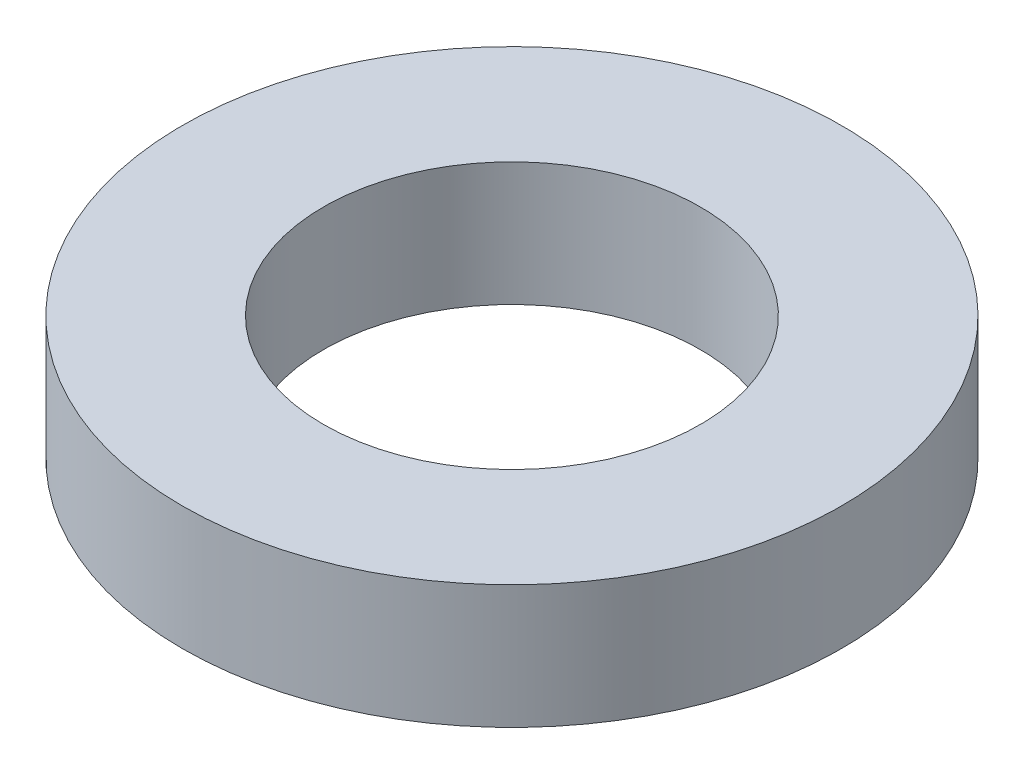
SolidWorks part; units mm, degrees
ref_plane "Front" through (0, 0, 0) normal (0, 0, 1) x (1, 0, 0)
ref_plane "Top" through (0, 0, 0) normal (0, 1, 0) x (1, 0, 0)
ref_plane "Right" through (0, 0, 0) normal (1, 0, 0) x (0, 0, -1)
sketch "Sketch1" plane through (0, 0, 0) normal (0, 1, 0) x (1, 0, 0)
  circle A0 centre (0, 0) radius 5.334
  circle A1 centre (0, 0) radius 3.05
  dimension "D1" = 10.668
  dimension "D2" = 6.1
extrude "Boss-Extrude1" add sketch "Sketch1" along normal blind 2
